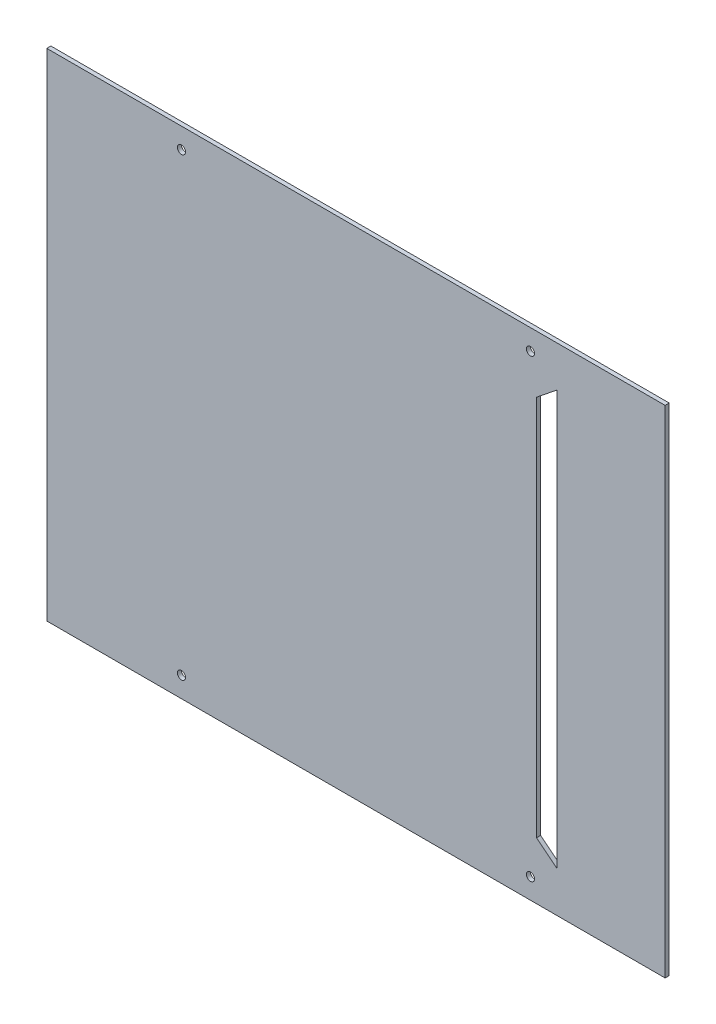
SolidWorks part; units mm, degrees
ref_plane "Front Plane" through (0, 0, 0) normal (0, 0, 1) x (1, 0, 0)
ref_plane "Top Plane" through (0, 0, 0) normal (0, 1, 0) x (1, 0, 0)
ref_plane "Right Plane" through (0, 0, 0) normal (1, 0, 0) x (0, 0, -1)
sketch "Sketch1" plane through (0, 0, 0) normal (0, 0, 1) x (1, 0, 0)
  line L0 (0, 0) -> (-206.9982, 0) construction
  line L1 (151.5, -121.5) -> (-151.5, -121.5)
  line L2 (151.5, -121.5) -> (151.5, 121.5)
  line L3 (151.5, 121.5) -> (-151.5, 121.5)
  line L4 (-151.5, -121.5) -> (-151.5, 121.5)
  line L5 (151.5, -121.5) -> (-151.5, 121.5) construction
  line L6 (151.5, 121.5) -> (-151.5, -121.5) construction
  line L7 (139.0309, -111.5) -> (-139.0309, -111.5) construction
  line L8 (139.0309, -111.5) -> (139.0309, 111.5) construction
  line L9 (139.0309, 111.5) -> (-139.0309, 111.5) construction
  line L10 (-139.0309, -111.5) -> (-139.0309, 111.5) construction
  line L11 (139.0309, -111.5) -> (-139.0309, 111.5) construction
  line L12 (139.0309, 111.5) -> (-139.0309, -111.5) construction
  line L13 (98.5, 101.5) -> (98.5, -101.5)
  line L14 (88.5, 93.4802) -> (88.5, -93.4802)
  line L15 (98.5, 101.5) -> (88.5, 93.4802)
  line L16 (98.5, -101.5) -> (88.5, -93.4802)
  circle A0 centre (-85.5, 111.5) radius 2
  circle A1 centre (85.5, 111.5) radius 2
  circle A2 centre (85.5, -111.5) radius 2
  circle A3 centre (-85.5, -111.5) radius 2
  point P0 (0, 0)
  point P5 (0, 0)
  dimension "D4" = 4
  dimension "D5" = 4
  dimension "D1" = 303
  dimension "D2" = 243
  dimension "D3" = 10
  dimension "D6" = 66
  dimension "D7" = 66
  dimension "D8" = 53
  dimension "D9" = 10
  dimension "D10" = 10
  dimension "D11" = 10
extrude "Boss-Extrude1" add sketch "Sketch1" along normal blind 2
